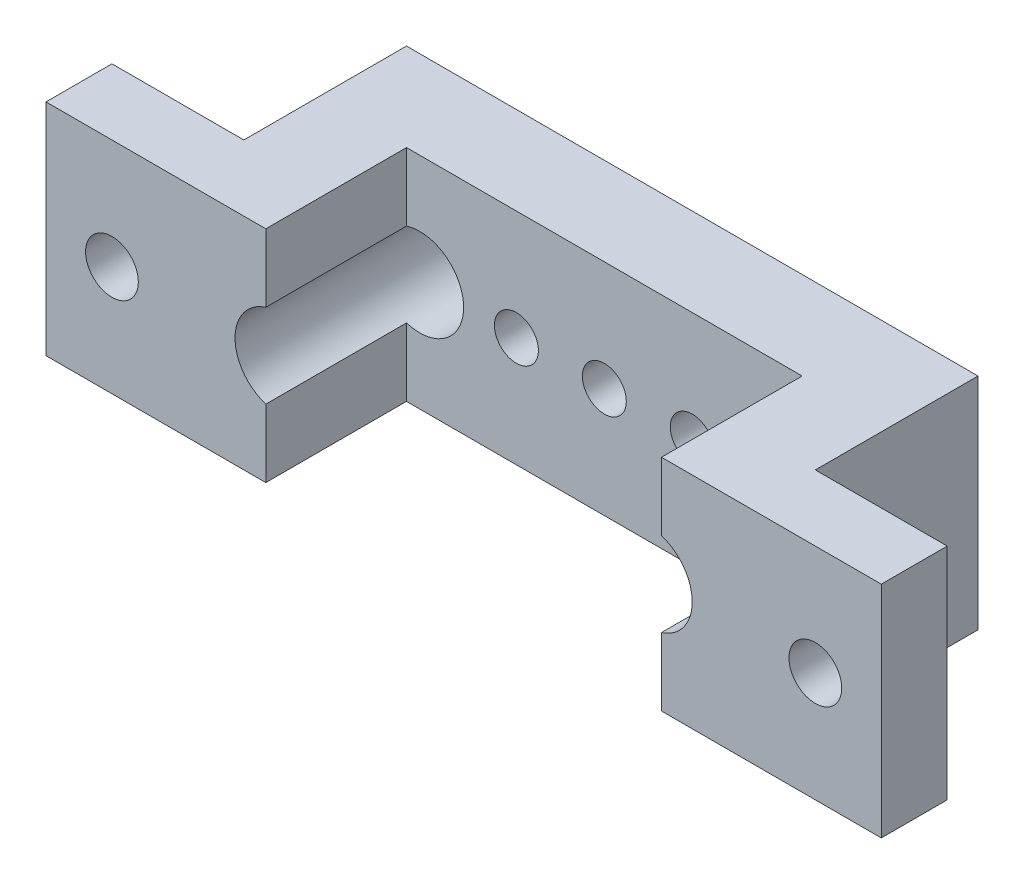
SolidWorks part; units mm, degrees
note: The reader was unsure of these and kept them because the rebuilt part matched: shared geometry of "草图1<10>", "草图1<13>".
ref_plane "前视基准面" through (0, 0, 0) normal (0, 0, 1) x (1, 0, 0)
ref_plane "上视基准面" through (0, 0, 0) normal (0, 1, 0) x (1, 0, 0)
ref_plane "右视基准面" through (0, 0, 0) normal (1, 0, 0) x (0, 0, -1)
other "Configuration Table"
sketch "草图1" plane through (0, 0, 0) normal (0, 0, 1) x (1, 0, 0)
  line L9 (-4.5, 2.5) -> (4.5, 2.5)
  line L10 (-4.5, 2.5) -> (-4.5, -2.5)
  line L11 (-4.5, -2.5) -> (4.5, -2.5)
  line L12 (4.5, 2.5) -> (4.5, -2.5)
  line L13 (-2, 0) -> (0, 0)
  line L14 (0, 0) -> (2, 0)
  line L22 (4.5, 2.5) -> (6.5, 2.5)
  line L23 (4.5, 2.5) -> (4.5, -2.5)
  line L24 (4.5, -2.5) -> (6.5, -2.5)
  line L25 (6.5, 2.5) -> (6.5, -2.5)
  line L26 (-4.5, 2.5) -> (-6.5, 2.5)
  line L27 (-4.5, 2.5) -> (-4.5, -2.5)
  line L28 (-4.5, -2.5) -> (-6.5, -2.5)
  line L29 (-6.5, 2.5) -> (-6.5, -2.5)
  line L34 (-6.5, 2.5) -> (-9.5, 2.5)
  line L35 (-6.5, 2.5) -> (-6.5, -2.5)
  line L36 (-6.5, -2.5) -> (-9.5, -2.5)
  line L37 (-9.5, 2.5) -> (-9.5, -2.5)
  line L38 (6.5, 2.5) -> (9.5, 2.5)
  line L39 (6.5, 2.5) -> (6.5, -2.5)
  line L40 (6.5, -2.5) -> (9.5, -2.5)
  line L41 (9.5, 2.5) -> (9.5, -2.5)
  circle A8 centre (-8, 0) radius 0.6
  circle A11 centre (8, 0) radius 0.6
  circle A12 centre (-2, 0) radius 0.5
  circle A13 centre (0, 0) radius 0.5
  circle A14 centre (2, 0) radius 0.5
  circle A15 centre (-4.2, 0) radius 1
  circle A16 centre (4.2, 0) radius 1
  point P4 (0, 2.5)
  point P6 (-4.5, 0)
  point P7 (0, 0)
  point P23 (0, 0)
  point P24 (0, 0)
  point P54 (-8, 2.5)
  point P56 (8, 2.5)
  dimension "D4" = 2.2
  dimension "D1" = 5
  dimension "D2" = 9
  dimension "D3" = 2
  dimension "D10" = 1.2
  dimension "D5" = 1
  dimension "D7" = 2
  dimension "D6" = 2
  dimension "D8" = 2.2
  dimension "D9" = 3
extrude "凸台-拉伸1" add sketch "草图1" along normal blind 2
extrude "凸台-拉伸2" add sketch "草图1<10>" along normal blind 5.2 contours L26 L29 L28 L10 | L25 L22 L12 L24
sketch "草图1<10>" plane through (0, 0, 0) normal (0, 0, 1) x (1, 0, 0) same geometry as "草图1"
extrude "凸台-拉伸3" add sketch "草图1<13>" against normal blind 1.5 from surface at 5.2 contours L34 L37 L36 L29 A8 | L41 L38 L25 L40 A11 starting at face at (-5.2833, 0, 5.2)
sketch "草图1<13>" plane through (0, 0, 0) normal (0, 0, 1) x (1, 0, 0) same geometry as "草图1"
